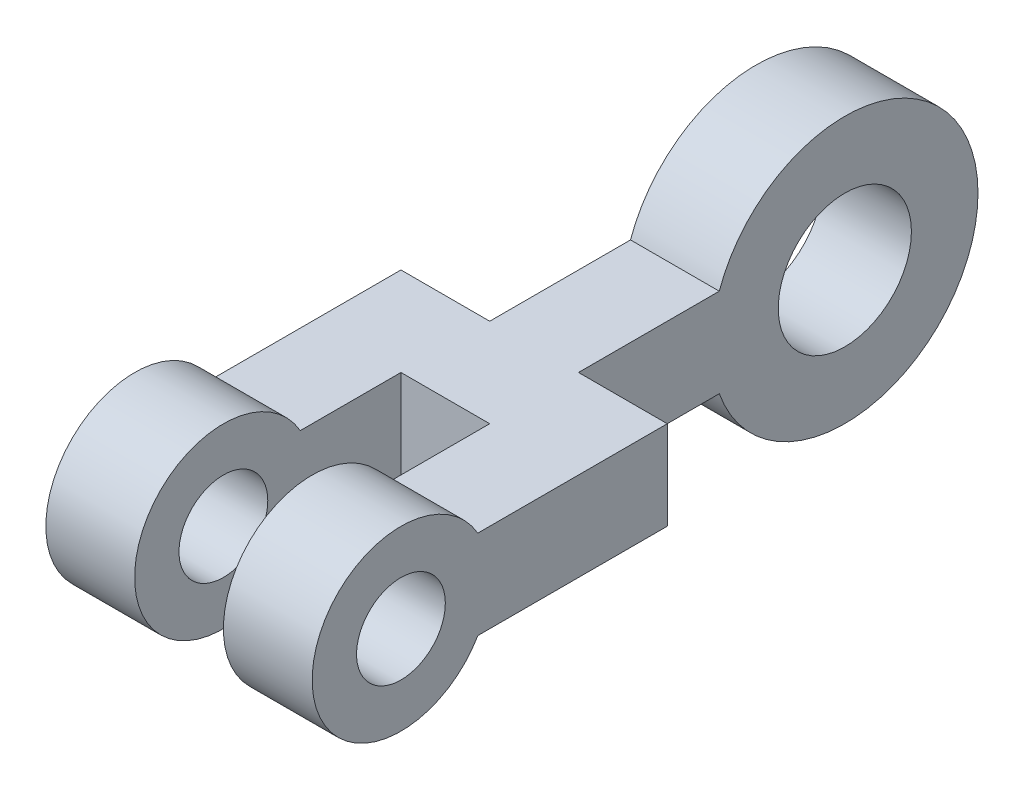
SolidWorks part; units mm, degrees
material "1060 Alloy"
ref_plane "Front Plane" through (0, 0, 0) normal (0, 0, 1) x (1, 0, 0)
ref_plane "Top Plane" through (0, 0, 0) normal (0, 1, 0) x (1, 0, 0)
ref_plane "Right Plane" through (0, 0, 0) normal (1, 0, 0) x (0, 0, -1)
sketch "Sketch1" plane through (0, 0, 0) normal (0, 1, 0) x (1, 0, 0)
  line L0 (0, 12.7) -> (12.7, 12.7)
  line L1 (12.7, 12.7) -> (12.7, 38.1)
  line L2 (12.7, 38.1) -> (25.4, 38.1)
  line L3 (25.4, 38.1) -> (25.4, 12.7)
  line L4 (25.4, 12.7) -> (38.1, 12.7)
  line L5 (38.1, 12.7) -> (38.1, 50.8)
  line L6 (38.1, 50.8) -> (25.4, 50.8)
  line L7 (25.4, 50.8) -> (25.4, 88.9)
  line L8 (25.4, 88.9) -> (12.7, 88.9)
  line L9 (12.7, 88.9) -> (12.7, 50.8)
  line L10 (12.7, 50.8) -> (0, 50.8)
  line L11 (0, 50.8) -> (0, 12.7)
  dimension "D1" = 12.7
  dimension "D2" = 12.7
  dimension "D3" = 12.7
  dimension "D4" = 76.2
  dimension "D5" = 25.4
  dimension "D6" = 12.7
  dimension "D7" = 12.7
extrude "Boss-Extrude1" add sketch "Sketch1" along normal mid plane 12.7
sketch "Sketch2" plane through (38.1, 0, 0) normal (1, 0, 0) x (0, 0, -1)
  line L0 (38.1, 6.35) -> (38.1, -6.35) construction
  circle A0 centre (12.7, 0) radius 6.35
  circle A1 centre (12.7, 0) radius 12.7
  circle A2 centre (88.9, 0) radius 9.525
  circle A3 centre (88.9, 0) radius 19.05
  line M1 (12.7, -6.35) -> (50.8, -6.35)
  line M3 (50.8, 6.35) -> (12.7, 6.35)
  line M4 (12.7, 6.35) -> (12.7, -6.35)
  dimension "D1" = 12.7
  dimension "D2" = 25.4
  dimension "D3" = 19.05
  dimension "D4" = 38.1
  dimension "D5" = 76.2
  dimension "D6" = 25.4
extrude "Boss-Extrude2" add sketch "Sketch2" against normal blind 12.7 contours A1 M3 | A1 A0 M1 M3 | A1 M1 | A1 A0 M3 M1 region at (38.1, 0, -21.1455) region at (38.1, 0, -6.0026)
extrude "Boss-Extrude4" add sketch "Sketch2<3>" against normal blind 12.7 from offset 25.4 contours A1 A0 M3 M1 | A1 M3 | A1 A0 M1 M3 | A1 M1 region at (38.1, 0, -21.1455) region at (38.1, 0, -6.0026) offset against normal yes
sketch "Sketch2<3>" plane through (38.1, 0, 0) normal (1, 0, 0) x (0, 0, -1) same geometry as "Sketch2"
extrude "Boss-Extrude5" add sketch "Sketch2<4>" against normal blind 12.7 from offset 12.7 contours A3 A2 region at (38.1, 0, -70.3888) offset against normal yes
sketch "Sketch2<4>" plane through (38.1, 0, 0) normal (1, 0, 0) x (0, 0, -1) same geometry as "Sketch2"
extrude "Cut-Extrude1" cut sketch "Sketch2<5>" against normal through all contours A0 | A2 | A0 M4 region at (38.1, 0, -15.395) region at (38.1, 0, -88.9)
sketch "Sketch2<5>" plane through (38.1, 0, 0) normal (1, 0, 0) x (0, 0, -1) same geometry as "Sketch2"
